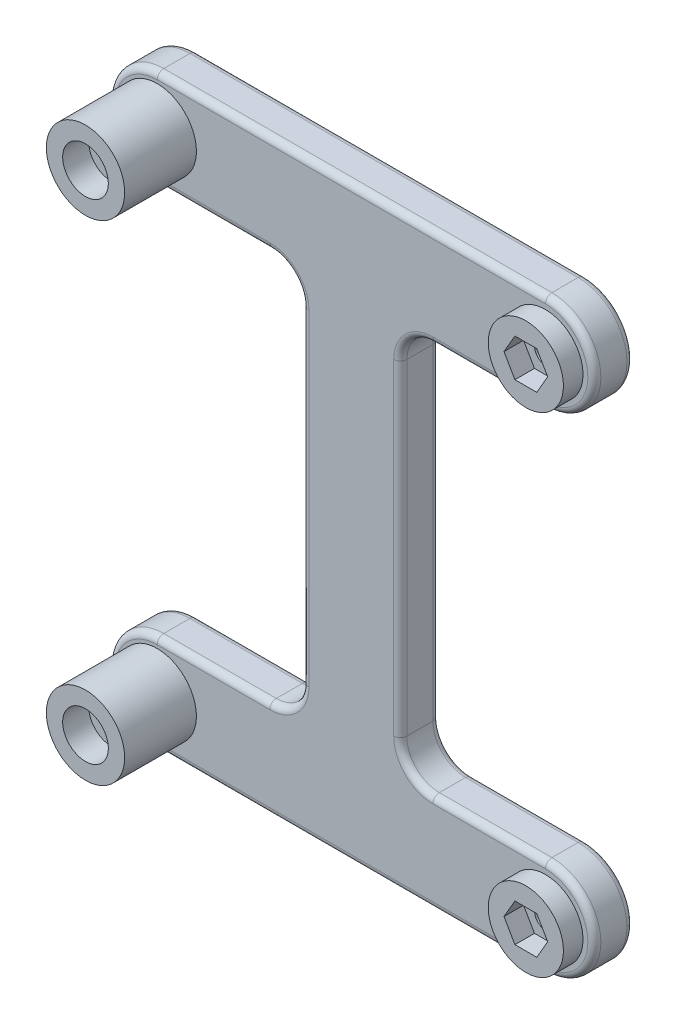
SolidWorks part; units mm, degrees
ref_plane "Front Plane" through (0, 0, 0) normal (0, 0, 1) x (1, 0, 0)
ref_plane "Top Plane" through (0, 0, 0) normal (0, 1, 0) x (1, 0, 0)
ref_plane "Right Plane" through (0, 0, 0) normal (1, 0, 0) x (0, 0, -1)
sketch "Sketch1" plane through (0, 0, 0) normal (0, 0, 1) x (1, 0, 0)
  line L85 (42.25, 7.5) -> (59.5, 7.5)
  line L97 (0, 82.5) -> (59.5, 82.5)
  line L98 (0, -7.5) -> (59.5, -7.5)
  line L99 (0, 67.5) -> (17.25, 67.5)
  line L100 (0, 7.5) -> (17.25, 7.5)
  line L101 (22.25, 62.5) -> (22.25, 12.5)
  line L106 (37.25, 62.5) -> (37.25, 12.5)
  line L107 (42.25, 67.5) -> (59.5, 67.5)
  circle A33 centre (0, 0) radius 4.5
  circle A57 centre (0, 75) radius 4.5
  circle A64 centre (59.5, 75) radius 1.65
  circle A65 centre (59.5, 0) radius 1.65
  arc A66 (0, 82.5) -> (0, 67.5) centre (0, 75) ccw
  arc A67 (0, 7.5) -> (0, -7.5) centre (0, 0) ccw
  arc A68 (59.5, 67.5) -> (59.5, 82.5) centre (59.5, 75) ccw
  arc A69 (59.5, -7.5) -> (59.5, 7.5) centre (59.5, 0) ccw
  arc A74 (37.25, 62.5) -> (42.25, 67.5) centre (42.25, 62.5) cw
  arc A75 (22.25, 62.5) -> (17.25, 67.5) centre (17.25, 62.5) ccw
  arc A76 (37.25, 12.5) -> (42.25, 7.5) centre (42.25, 12.5) ccw
  arc A77 (22.25, 12.5) -> (17.25, 7.5) centre (17.25, 12.5) cw
extrude "Boss-Extrude1" add sketch "Sketch1" along normal blind 6
sketch "Sketch2" plane through (0, 0, 6) normal (0, 0, 1) x (1, 0, 0)
  circle A0 centre (0, 75) radius 6
  circle A1 centre (0, 75) radius 3.5
  circle A2 centre (0, 0) radius 3.5
  circle A3 centre (0, 0) radius 6
extrude "Boss-Extrude2" add sketch "Sketch2" along normal blind 12 from offset 1 offset against normal yes
sketch "Sketch3" plane through (0, 0, 0) normal (0, 0, -1) x (-1, 0, 0)
  circle A0 centre (0, 75) radius 3.5
  circle A1 centre (0, 75) radius 1.65
  circle A2 centre (0, 0) radius 3.5
  circle A3 centre (0, 0) radius 1.65
extrude "Boss-Extrude3" add sketch "Sketch3" against normal offset from surface (8 mm away) 4 from offset 5 up to face at (6, 75, 17) offset against normal yes
sketch "Sketch4" plane through (0, 0, 6) normal (0, 0, 1) x (1, 0, 0)
  line L41 (62.8486, 75) -> (61.1743, 77.9)
  line L42 (61.1743, 77.9) -> (57.8257, 77.9)
  line L43 (57.8257, 77.9) -> (56.1514, 75)
  line L44 (56.1514, 75) -> (57.8257, 72.1)
  line L45 (57.8257, 72.1) -> (61.1743, 72.1)
  line L46 (61.1743, 72.1) -> (62.8486, 75)
  line L47 (62.8486, 0) -> (61.1743, 2.9)
  line L48 (61.1743, 2.9) -> (57.8257, 2.9)
  line L49 (57.8257, 2.9) -> (56.1514, 0)
  line L50 (56.1514, 0) -> (57.8257, -2.9)
  line L51 (57.8257, -2.9) -> (61.1743, -2.9)
  line L52 (61.1743, -2.9) -> (62.8486, 0)
  circle A6 centre (59.5, 0) radius 5.76
  circle A7 centre (59.5, 75) radius 5.76
extrude "Boss-Extrude4" add sketch "Sketch4" along normal blind 3
fillet "Fillet1" radius 1 32 edges at (-7.5, 0, 0) (8.625, 7.5, 0) (20.7855, 8.9645, 0) (22.25, 37.5, 0) (20.7855, 66.0355, 0) (8.625, 67.5, 0) (-7.5, 75, 0) (29.75, 82.5, 0) (67, 75, 0) (50.875, 67.5, 0) (38.7145, 66.0355, 0) (37.25, 37.5, 0) (38.7145, 8.9645, 0) (50.875, 7.5, 0) (67, 0, 0) (-7.5, 0, 6) (8.625, 7.5, 6) (20.7855, 8.9645, 6) (22.25, 37.5, 6) (20.7855, 66.0355, 6) (8.625, 67.5, 6) (-7.5, 75, 6) (29.75, 82.5, 6) (67, 75, 6) (50.875, 67.5, 6) (38.7145, 66.0355, 6) (37.25, 37.5, 6) (38.7145, 8.9645, 6) (50.875, 7.5, 6) (67, 0, 6) (29.75, -7.5, 0) (29.75, -7.5, 6)
